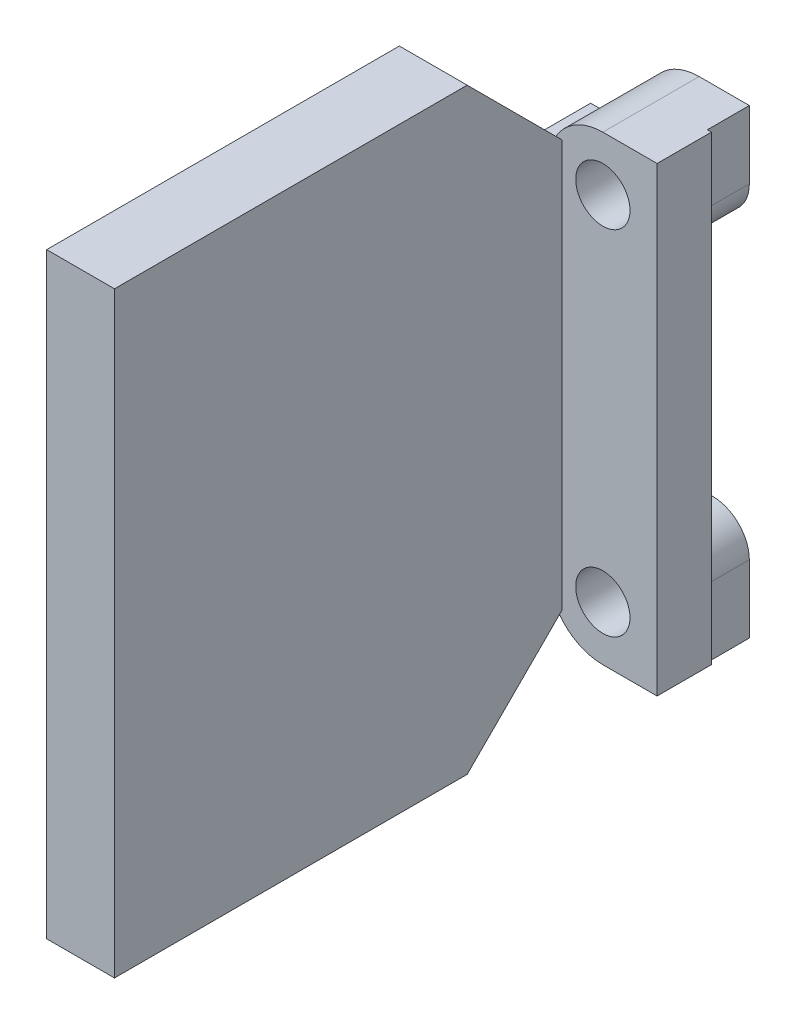
SolidWorks part; units mm, degrees
ref_plane "Top Plane" through (0, 0, 0) normal (0, 0, 1) x (1, 0, 0)
ref_plane "Right Plane" through (0, 0, 0) normal (0, 1, 0) x (1, 0, 0)
ref_plane "Front Plane" through (0, 0, 0) normal (1, 0, 0) x (0, 0, -1)
sketch "Sketch1" plane through (0, 0, 0) normal (0, 0, 1) x (1, 0, 0)
  line L0 (-44, 0) -> (-44, 9)
  line L12 (-36, 17) -> (-32, 17)
  line L13 (-32, 12) -> (-32, 24.9289) construction
  line L15 (-32, 0) -> (-32, 17)
  line L17 (-44, 9) -> (-44, -9) construction
  line L18 (-44, 0) -> (-32, 0)
  arc A0 (-36, 17) -> (-40, 13) centre (-36, 13) ccw construction
  arc A3 (-43.995, 9) -> (-40, 13) centre (-44, 13) ccw construction
  arc A4 (-36, 17) -> (-40, 13) centre (-36, 13) ccw
  arc A5 (-44, 9) -> (-40, 13) centre (-44, 13) ccw
  circle A8 centre (-36, 13) radius 2 construction
  circle A9 centre (-36, 13) radius 2
  point P0 (-44, 8.8732)
extrude "Boss-Extrude1" add sketch "Sketch1" along normal blind 4
sketch "Sketch2" plane through (0, 0, 0) normal (0, 0, -1) x (-1, 0, 0)
  line L0 (32, 12) -> (32, 24.9289) construction
  line L1 (35, 9) -> (44, 9) construction
  line L2 (32, 12) -> (32, 24.9289) construction
  line L3 (35, 9) -> (44, 9) construction
  line L4 (35, 9.3) -> (42.4801, 9.3)
  line L5 (32.3, 12) -> (32.3, 17)
  line L6 (36, 17) -> (32.3, 17)
  line L7 (32.3, 12) -> (32.3, 24.9289) construction
  line L8 (35, 9.3) -> (44, 9.3) construction
  line L9 (32, 17) -> (36, 17) construction
  arc A0 (32, 12) -> (35, 9) centre (35, 12) ccw construction
  arc A1 (32, 12) -> (35, 9) centre (35, 12) ccw construction
  arc A2 (32.3, 12) -> (35, 9.3) centre (35, 12) ccw
  arc A3 (40, 13) -> (43.995, 9) centre (44, 13) ccw construction
  arc A4 (40, 13) -> (36, 17) centre (36, 13) ccw construction
  arc A6 (40, 13) -> (42.4801, 9.3) centre (44, 13) ccw
  arc A7 (40, 13) -> (36, 17) centre (36, 13) ccw
  circle A9 centre (36, 13) radius 2 construction
  circle A10 centre (36, 13) radius 2
  dimension "D1" = 0.3
extrude "Boss-Extrude2" add sketch "Sketch2" along normal offset from surface (3.1 mm away) 0.1
sketch "Sketch4" plane through (-44, -0.0245, 0) normal (1, 0, 0) x (0, 0, 1)
  line L1 (0.3, -11.3245) -> (11, -22.0245)
  line L2 (11, -22.0245) -> (37, -22.0245)
  line L3 (37, -22.0245) -> (37, -0.0245)
  line L4 (37, -0.0245) -> (0, -0.0245)
  line L6 (0.3, -11.3245) -> (11, -11.3245) construction
  line L7 (11, -11.3245) -> (11, -22.0245) construction
  line L9 (-3, -9.0245) -> (-3, 8.9755) construction
  line L10 (0, -9.3245) -> (0, -0.0245)
  line L11 (0, -9.3245) -> (-3.1, -9.3245)
  line L12 (-3.1, -9.3245) -> (-3.1, -11.3245)
  line L13 (-3.1, -11.3245) -> (0.3, -11.3245)
  line L14 (-3.1, -9.3245) -> (0, -9.3245) construction
  point P14 (0, 0)
  dimension "D1" = 40
  dimension "D2" = 26
  dimension "D3" = 22
  dimension "D4" = 2
extrude "Boss-Extrude3" add sketch "Sketch4" along normal blind 5
mirror "Mirror1" about plane through (-44, 0, 4) normal (0, 1, 0) of bodies 104
